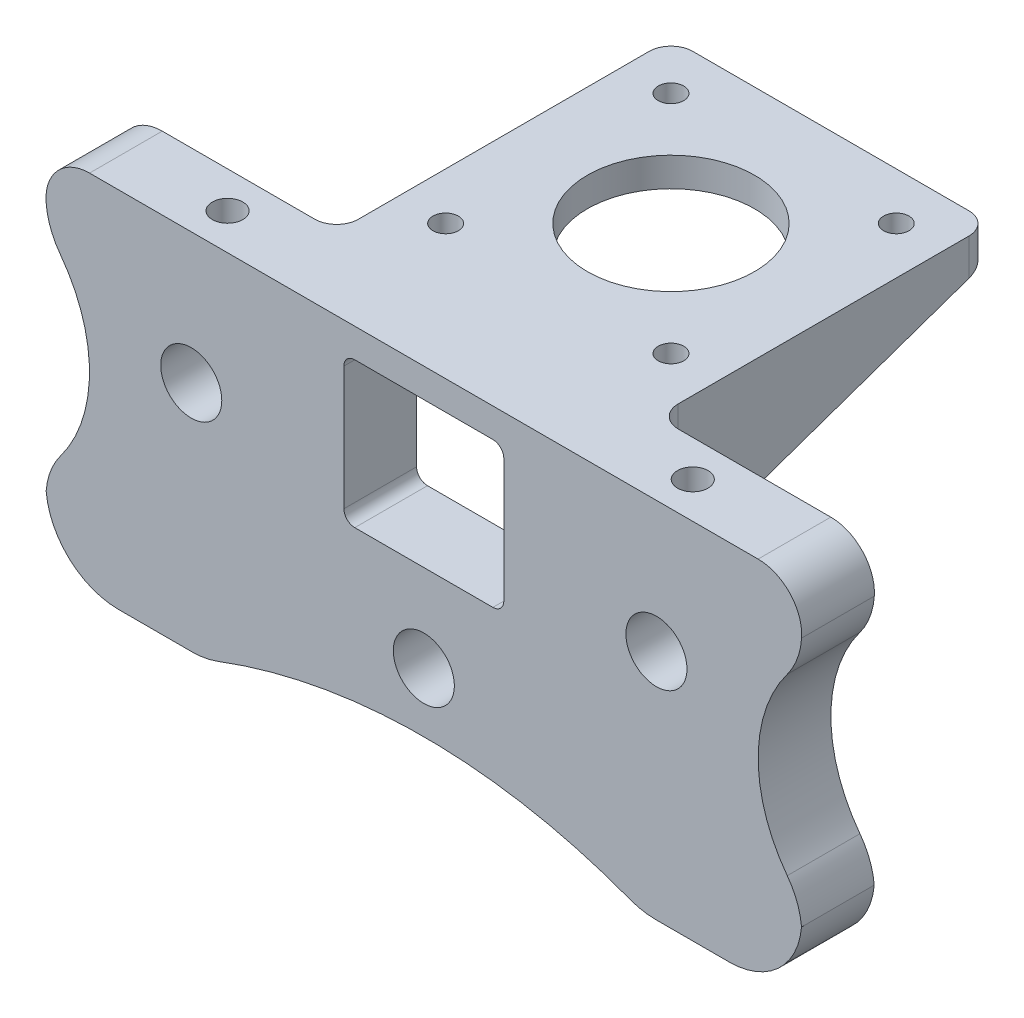
SolidWorks part; units mm, degrees
ref_plane "Front Plane" through (0, 0, 0) normal (0, 0, 1) x (1, 0, 0)
ref_plane "Top Plane" through (0, 0, 0) normal (0, 1, 0) x (1, 0, 0)
ref_plane "Right Plane" through (0, 0, 0) normal (1, 0, 0) x (0, 0, -1)
sketch "Sketch1" plane through (0, 0, 0) normal (0, 0, 1) x (1, 0, 0)
  line L0 (-52, 25) -> (52, -25) construction
  line L1 (-52, 25) -> (52, 25)
  line L2 (-52, 25) -> (-52, 15.5657)
  line L3 (-52, -25) -> (-30, -25)
  line L4 (52, 25) -> (52, 15.5657)
  line L5 (0, 0) -> (0, 48.9699) construction
  line L6 (-52, -13) -> (-52, -25)
  line L7 (52, -13) -> (52, -25)
  line L8 (30, -25) -> (52, -25)
  line L9 (-9.5, 21) -> (9.5, 21)
  line L10 (11, 19.5) -> (11, 2.5)
  line L11 (9.5, 1) -> (-9.5, 1)
  line L12 (-11, 2.5) -> (-11, 19.5)
  arc A0 (-52, 15.5657) -> (-52, -13) centre (-66, 1.2829) cw
  arc A1 (52, 15.5657) -> (52, -13) centre (66, 1.2829) ccw
  arc A2 (-30, -25) -> (30, -25) centre (0, -99.162) cw
  circle A3 centre (0, -11) radius 4.2
  circle A4 centre (-32, 7) radius 4.2
  circle A5 centre (32, 7) radius 4.2
  arc A6 (-9.5, 1) -> (-11, 2.5) centre (-9.5, 2.5) cw
  arc A7 (11, 2.5) -> (9.5, 1) centre (9.5, 2.5) cw
  arc A8 (9.5, 21) -> (11, 19.5) centre (9.5, 19.5) cw
  arc A9 (-9.5, 21) -> (-11, 19.5) centre (-9.5, 19.5) ccw
  point P4 (0, 0)
  dimension "D3" = 20
  dimension "D7" = 18
  dimension "D8" = 8.4
  dimension "D14" = 1.5
  dimension "D17" = 80
  dimension "D1" = 50
  dimension "D2" = 104
  dimension "D4" = 14
  dimension "D5" = 14
  dimension "D6" = 60
  dimension "D9" = 64
  dimension "D10" = 18
  dimension "D11" = 22
  dimension "D12" = 20
  dimension "D13" = 4
  dimension "D15" = 12
extrude "Boss-Extrude1" add sketch "Sketch1" along normal mid plane 10
fillet "Fillet1" radius 10 8 edges at (52, 15.5657, 0) (52, -13, 0) (52, -25, 0) (30, -25, 0) (-30, -25, 0) (-52, -25, 0) (-52, -13, 0) (-52, 15.5657, 0)
fillet "Fillet2" radius 6 2 edges at (52, 25, 0) (-52, 25, 0)
sketch "Sketch2" plane through (0, 25, -30) normal (0, 1, 0) x (-1, 0, 0)
  line L0 (-45.99, 25) -> (45.99, 25) construction
  line L1 (-21, 25) -> (21, 25)
  line L2 (-21, 25) -> (-21, -21)
  line L3 (-21, -21) -> (21, -21)
  line L4 (21, 25) -> (21, -21)
  line L5 (0, 30) -> (0, 51.7954) construction
  line L6 (0, 1) -> (0, 20.5767) construction
  line L7 (0, 1) -> (-18.4581, 1) construction
  circle A1 centre (0, 1) radius 11.5
  circle A2 centre (15.5, 16.5) radius 1.75
  circle A3 centre (-15.5, 16.5) radius 1.75
  circle A4 centre (-15.5, -14.5) radius 1.75
  circle A5 centre (15.5, -14.5) radius 1.75
  dimension "D3" = 22
  dimension "D4" = 23
  dimension "D5" = 31
  dimension "D7" = 3.5
  dimension "D1" = 46
  dimension "D2" = 42
  dimension "D6" = 31
  dimension "D8" = 6.5
extrude "Boss-Extrude2" add sketch "Sketch2" against normal blind 4
sketch "Sketch3" plane through (0, 21, 0) normal (0, -1, 0) x (1, 0, 0)
  circle A0 centre (-15.5, -44.5) radius 3
  circle A1 centre (15.5, -44.5) radius 3
  circle A2 centre (15.5, -13.5) radius 3
  circle A3 centre (-15.5, -13.5) radius 3
  dimension "D1" = 6
extrude "Cut-Extrude1" cut sketch "Sketch3" along normal up to next from offset 1 offset against normal yes
sketch "Sketch4" plane through (0, 25, 0) normal (0, 1, 0) x (1, 0, 0)
  line L0 (0, 0) -> (0, 64.113) construction
  circle A0 centre (-32, 0) radius 1.75
  circle A1 centre (32, 0) radius 1.75
  dimension "D1" = 64
  dimension "D2" = 3.5
extrude "Cut-Extrude2" cut sketch "Sketch4" against normal up to next
sketch "Sketch5" plane through (0, 25, 0) normal (0, 1, 0) x (1, 0, 0)
  circle A0 centre (-32, 0) radius 2.1
  circle A1 centre (32, 0) radius 2.1
  dimension "D1" = 4.2
extrude "Cut-Extrude3" cut sketch "Sketch5" against normal blind 4
chamfer "Chamfer1" distance 0.5 angle 45 2 edges at (-32, 21, 1.75) (32, 21, 1.75)
sketch "Sketch6" plane through (-21, 0, 0) normal (-1, 0, 0) x (0, 0, 1)
  line L0 (-51, 25) -> (-5, 25)
  line L1 (-5, 25) -> (-5, 5)
  line L2 (-5, 13.2829) -> (-5, -10.7171) construction
  line L3 (-5, 5) -> (-51, 21)
  line L4 (-51, 21) -> (-51, 25)
  dimension "D1" = 20
  dimension "D2" = 4
extrude "Boss-Extrude3" add sketch "Sketch6" against normal blind 2 and the other way blind 1
mirror "Mirror1" about plane through (0, 0, 0) normal (1, 0, 0) of "Boss-Extrude3"
fillet "Fillet3" radius 2 2 edges at (-14.25, 21, -5) (14.25, 21, -5)
fillet "Fillet4" radius 3 4 edges at (-22, 23, -51) (22, 23, -51) (-22, 15, -5) (22, 15, -5)
